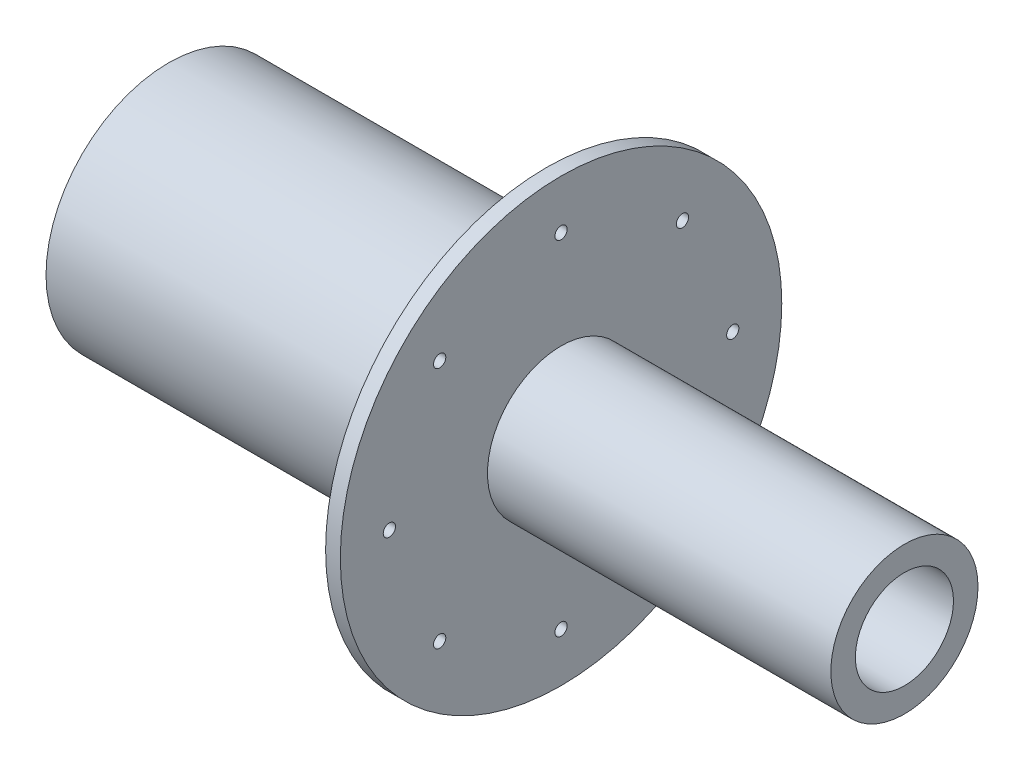
SolidWorks part; units mm, degrees
ref_plane "Front Plane" through (0, 0, 0) normal (0, 0, 1) x (1, 0, 0)
ref_plane "Top Plane" through (0, 0, 0) normal (0, 1, 0) x (1, 0, 0)
ref_plane "Right Plane" through (0, 0, 0) normal (1, 0, 0) x (0, 0, -1)
sketch "Sketch1" plane through (0, 0, 0) normal (1, 0, 0) x (0, 0, -1)
  circle A0 centre (0, 0) radius 10
  circle A1 centre (0, 0) radius 15
  circle A2 centre (0, 0) radius 25
  circle A3 centre (0, 0) radius 45
  dimension "D1" = 50
  dimension "D2" = 30
  dimension "D3" = 20
  dimension "D4" = 90
extrude "Boss-Extrude1" add sketch "Sketch1" against normal blind 80 contours A1 A0 | A2 A1 region at (0, 0, 14.5757) region at (0, 0, 24.2929)
extrude "Boss-Extrude2" add sketch "Sketch1<3>" along normal blind 70 separate body contours A1 A0 region at (0, 0, 14.5757)
sketch "Sketch1<3>" plane through (0, 0, 0) normal (1, 0, 0) x (0, 0, -1) same geometry as "Sketch1"
extrude "Boss-Extrude3" add sketch "Sketch1<4>" against normal blind 3 contours A3 A2 region at (0, 0, 43.7272)
sketch "Sketch1<4>" plane through (0, 0, 0) normal (1, 0, 0) x (0, 0, -1) same geometry as "Sketch1"
hole_wizard "M3 Tapped Hole1" positions "Sketch2" profile "Sketch3" tap size "M3" standard "ISO" end condition through all
sketch "Sketch2" plane through (-3, 0, 0) normal (-1, 0, 0) x (0, 0, 1)
  line L0 (0, 0) -> (0, -45) construction
  line L1 (0, -45) -> (0, 45) construction
  line L2 (0, 45) -> (0, 0) construction
  line L3 (0, 0) -> (45, 0) construction
  line L4 (45, 0) -> (-45, 0) construction
  line L5 (-45, 0) -> (0, 0) construction
  line L6 (0, 0) -> (-31.8198, -31.8198) construction
  line L7 (-31.8198, -31.8198) -> (31.8198, 31.8198) construction
  line L8 (31.8198, 31.8198) -> (0, 0) construction
  line L9 (0, 0) -> (31.8198, -31.8198) construction
  line L10 (31.8198, -31.8198) -> (-31.8198, 31.8198) construction
  circle A0 centre (0, 0) radius 45 construction
  circle A1 centre (0, 0) radius 35
  point P0 (35, 0)
  point P2 (0, 35)
  point P4 (-35, 0)
  point P6 (0, -35)
  point P8 (24.7487, 24.7487)
  point P10 (-24.7487, 24.7487)
  point P12 (-24.7487, -24.7487)
  point P14 (24.7487, -24.7487)
  point P70 (24.7487, 24.7487)
  point P71 (0, 35)
  point P72 (35, 0)
  point P73 (-24.7487, 24.7487)
  point P74 (-35, 0)
  point P75 (-24.7487, -24.7487)
  point P76 (0, -35)
  point P77 (24.7487, -24.7487)
sketch "Sketch3" plane through (-3, 0, 35) normal (0, 1, 0) x (0, 0, 1)
  line L0 (0, 0) -> (0, 73)
  line L1 (0, 73) -> (1.25, 73)
  line L2 (1.25, 73) -> (1.25, 0.275)
  line L3 (1.25, 0.275) -> (1.525, 0)
  line L5 (1.525, 0) -> (0, 0)
  line L6 (-1.25, 0.275) -> (-1.525, 0) construction
  line L11 (0, -6.35) -> (0, 107.95) construction
  dimension "Thru Tap Drill Dia." = 2.5
  dimension "Thru Tap Drill Depth" = 73
  dimension "Near C'Sink Dia." = 3.05
  dimension "Near C'Sink Angle" = 90
cosmetic thread "Hole Thread1" parameters "D2"=3
cosmetic thread "Hole Thread2" parameters "D2"=3
cosmetic thread "Hole Thread3" parameters "D2"=3
cosmetic thread "Hole Thread4" parameters "D2"=3
cosmetic thread "Hole Thread5" parameters "D2"=3
cosmetic thread "Hole Thread6" parameters "D2"=3
cosmetic thread "Hole Thread7" parameters "D2"=3
cosmetic thread "Hole Thread8" parameters "D2"=3
